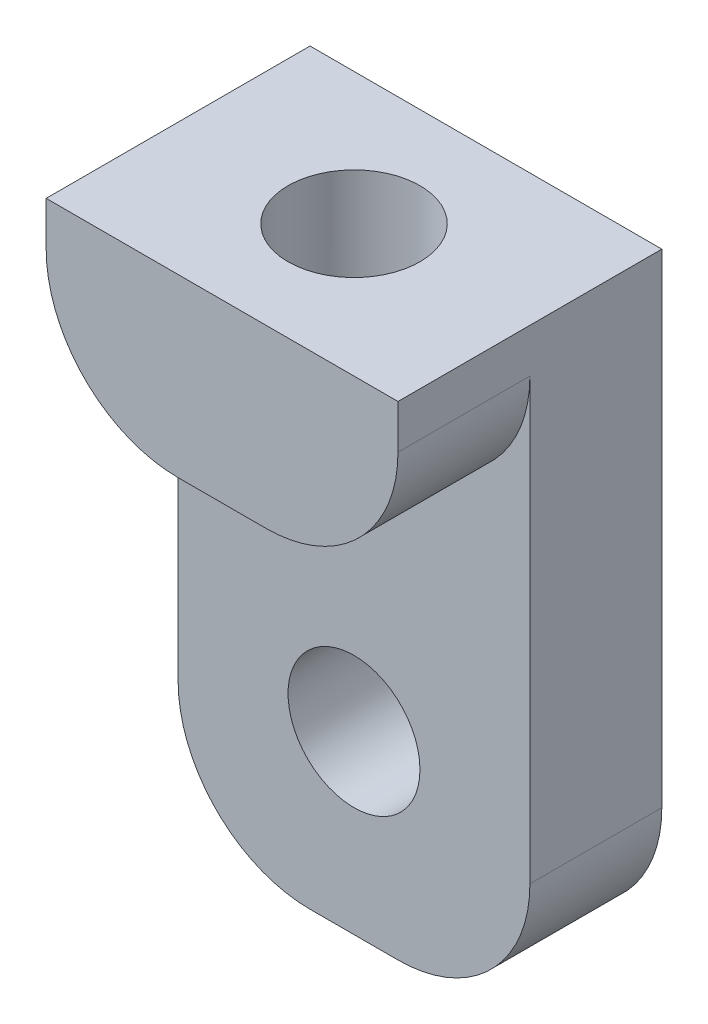
SolidWorks part; units mm, degrees
material "ABS"
ref_plane "Front Plane" through (0, 0, 0) normal (0, 0, 1) x (1, 0, 0)
ref_plane "Top Plane" through (0, 0, 0) normal (0, 1, 0) x (1, 0, 0)
ref_plane "Right Plane" through (0, 0, 0) normal (1, 0, 0) x (0, 0, -1)
sketch "Sketch1" plane through (0, 0, 0) normal (0, 0, 1) x (1, 0, 0)
  line L1 (-20, 50) -> (20, 50)
  line L2 (-20, 50) -> (-20, -20)
  line L3 (-20, -20) -> (20, -20)
  line L4 (20, 50) -> (20, -20)
  circle A0 centre (0, 0) radius 7.5
  point P9 (0, -20)
  dimension "D1" = 15
  dimension "D2" = 20
  dimension "D3" = 70
  dimension "D4" = 40
extrude "Boss-Extrude1" add sketch "Sketch1" along normal blind 30
sketch "Sketch2" plane through (0, 50, 0) normal (0, 1, 0) x (1, 0, 0)
  line L0 (-20, 0) -> (20, -30) construction
  line L4 (20, 0) -> (-20, 0)
  line L5 (-20, 0) -> (-20, -30)
  line L6 (-20, -30) -> (20, -30)
  line L7 (20, -30) -> (20, 0)
  line L8 (20, 0) -> (-20, 0)
  line L9 (-20, 0) -> (-20, -30)
  line L10 (-20, -30) -> (20, -30)
  line L11 (20, -30) -> (20, 0)
  circle A0 centre (0, -15) radius 7.5
  dimension "D2" = 15
  dimension "D1" = 0
extrude "Cut-Extrude1" cut sketch "Sketch2" against normal blind 20 contours L0 A0 | A0 L0 region at (1.9099, 50, 12.4535) region at (-1.9099, 50, 17.5465)
sketch "Sketch3" plane through (0, 0, 30) normal (0, 0, 1) x (1, 0, 0)
  line L0 (20, -20) -> (20, 50) construction
  line L1 (-20, -20) -> (20, -20)
  line L2 (-20, -20) -> (-20, 30)
  line L3 (-20, 30) -> (20, 30)
  line L4 (20, -20) -> (20, 30)
  dimension "D1" = 50
extrude "Cut-Extrude2" cut sketch "Sketch3" against normal blind 15 contours L2 L3 L4 L1
fillet "Fillet1" radius 15 4 edges at (-20, 30, 22.5) (20, 30, 22.5) (20, -20, 7.5) (-20, -20, 7.5)
